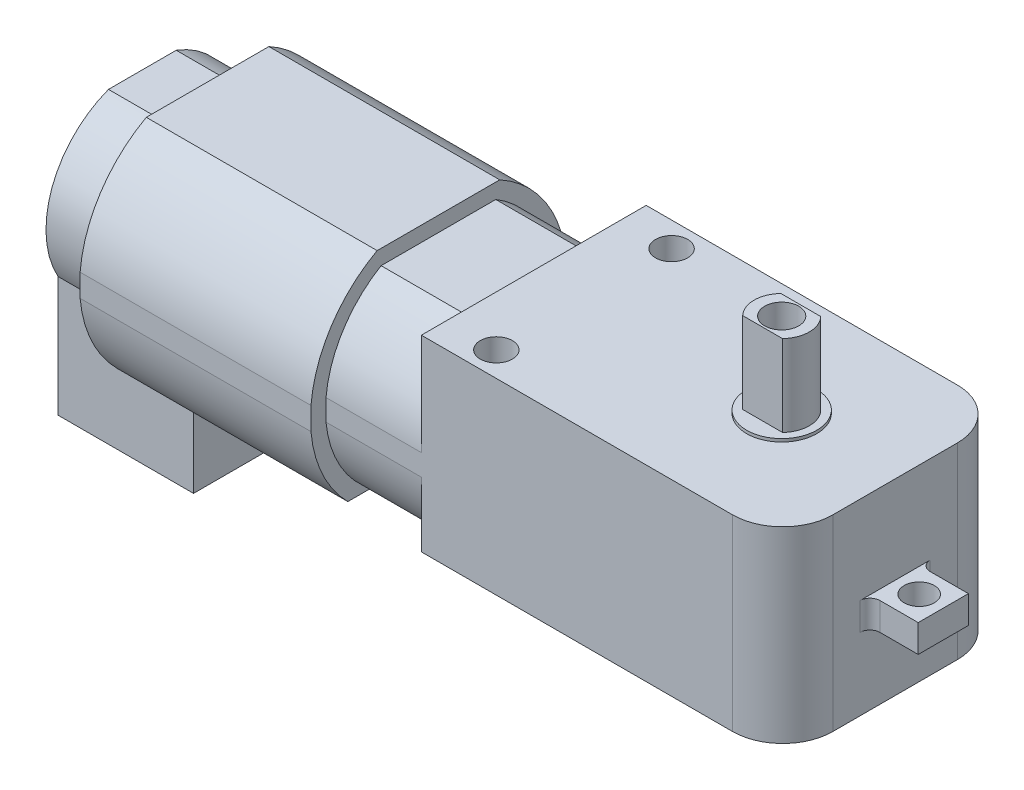
SolidWorks part; units mm, degrees
ref_plane "Front Plane" through (0, 0, 0) normal (0, 0, 1) x (1, 0, 0)
ref_plane "Top Plane" through (0, 0, 0) normal (0, 1, 0) x (1, 0, 0)
ref_plane "Right Plane" through (0, 0, 0) normal (1, 0, 0) x (0, 0, -1)
sketch "Sketch1" plane through (0, 0, 0) normal (0, 1, 0) x (1, 0, 0)
  line L0 (-13, -8.7312) -> (-13, 8.7312) construction
  line L1 (-18, -11.2) -> (18, -11.2)
  line L2 (-18, -11.2) -> (-18, 11.2)
  line L3 (-18, 11.2) -> (18, 11.2)
  line L4 (18, -11.2) -> (18, 11.2)
  line L5 (-18, -11.2) -> (18, 11.2) construction
  line L6 (-18, 11.2) -> (18, -11.2) construction
  circle A0 centre (-13, 8.7312) radius 1.6
  circle A1 centre (-13, -8.7312) radius 1.6
  point P0 (0, 0)
  point P8 (-13, 8.7312)
  point P9 (-13, 0)
  dimension "D3" = 3.2
  dimension "D1" = 36
  dimension "D2" = 22.4
  dimension "D4" = 31
  dimension "D5" = 8.7312
extrude "Boss-Extrude1" add sketch "Sketch1" along normal mid plane 18.7
fillet "Fillet1" radius 5 2 edges at (18, 0, 11.2) (18, 0, -11.2)
sketch "Sketch2" plane through (0, 9.35, 0) normal (0, 1, 0) x (1, 0, 0)
  line L0 (18, 0) -> (6.7, 0) construction
  line L1 (18, -6.2) -> (18, 6.2) construction
  circle A0 centre (6.7, 0) radius 3.5
  point P6 (10.2, 0)
  dimension "D1" = 7
  dimension "D2" = 7.8
extrude "Boss-Extrude2" add sketch "Sketch2" along normal blind 0.3
sketch "Sketch3" plane through (0, 9.65, 0) normal (0, 1, 0) x (1, 0, 0)
  line L0 (3.95, 0) -> (9.45, 0) construction
  line L1 (3.95, 1.905) -> (9.45, 1.905)
  line L2 (3.95, -1.905) -> (9.45, -1.905)
  circle A0 centre (6.7, 0) radius 2.75
  arc A1 (3.95, 1.905) -> (3.95, -1.905) centre (3.95, 0) ccw
  arc A2 (9.45, -1.905) -> (9.45, 1.905) centre (9.45, 0) ccw
  point P5 (6.7, 0)
  dimension "D1" = 5.5
  dimension "D2" = 3.81
extrude "Boss-Extrude4" add sketch "Sketch3" along normal offset from surface (8.4 mm away) 8.4 from surface contours A0 L0 L1 | L0 A0 L2 region at (6.7, 9.65, -0.9057) region at (6.7, 9.65, 0.9057) up to face at (6.7, 9.35, -3.5) offset beyond the face yes starting at face at (6.7, 9.35, -3.5)
sketch "Sketch4" plane through (0, 17.75, 0) normal (0, 1, 0) x (1, 0, 0)
  point P0 (6.7, 0)
hole_wizard "M3 Clearance Hole1" positions "3DSketch1" profile "Sketch6" hole size "M3" standard "ANSI Metric"
sketch3d "3DSketch1"
  point P0 (6.7, 17.75, 0)
sketch "Sketch6" plane through (6.7, 17.75, 0) normal (1, 0, 0) x (0, 0, 1)
  line L0 (0, 0) -> (0, 9.0215)
  line L1 (0, 9.0215) -> (1.7, 8)
  line L2 (1.7, 8) -> (1.7, 0)
  line L5 (1.7, 0) -> (0, 0)
  line L10 (0, 9.0215) -> (-1.7, 8) construction
  line L11 (0, -6.35) -> (0, 107.95) construction
  dimension "Hole Dia." = 3.4
  dimension "Hole Depth" = 8
  dimension "Drill Angle" = 118
sketch "Sketch7" plane through (-18, 0, 0) normal (-1, 0, 0) x (0, 0, 1)
  line L0 (11.2, 9.35) -> (11.2, -9.35) construction
  line L1 (-11.2, -9.35) -> (11.2, -9.35)
  line L2 (-11.2, -9.35) -> (-11.2, 7.85)
  line L3 (-11.2, 7.85) -> (11.2, 7.85)
  line L4 (11.2, -9.35) -> (11.2, 7.85)
  circle A0 centre (0, -1.8422) radius 11.25
  dimension "D2" = 22.5
  dimension "D1" = 17.2
extrude "Boss-Extrude5" add sketch "Sketch7" along normal blind 9.5 contours L4 A0 L3 L2 L1 region at (-18, -1.059, 0)
sketch "Sketch8" plane through (-27.5, 0, 0) normal (-1, 0, 0) x (0, 0, 1)
  line L8 (12.7, -2.9702) -> (12.7, -0.7141)
  line L9 (6.1072, 9.35) -> (-6.1072, 9.35)
  line L10 (-12.7, -0.7141) -> (-12.7, -2.9702)
  line L11 (-9.0234, -10.85) -> (9.0234, -10.85)
  line L12 (12.7, -2.9702) -> (12.7, -0.7141)
  line L13 (6.1072, 9.35) -> (-6.1072, 9.35)
  line L14 (-12.7, -0.7141) -> (-12.7, -2.9702)
  line L15 (-9.0234, -10.85) -> (9.0234, -10.85)
  arc A8 (12.7, -0.7141) -> (6.1072, 9.35) centre (0, -1.8422) ccw
  arc A9 (-6.1072, 9.35) -> (-12.7, -0.7141) centre (0, -1.8422) ccw
  arc A10 (-12.7, -2.9702) -> (-9.0234, -10.85) centre (0, -1.8422) ccw
  arc A11 (9.0234, -10.85) -> (12.7, -2.9702) centre (0, -1.8422) ccw
  arc A12 (12.7, -0.7141) -> (6.1072, 9.35) centre (0, -1.8422) ccw
  arc A13 (-6.1072, 9.35) -> (-12.7, -0.7141) centre (0, -1.8422) ccw
  arc A14 (-12.7, -2.9702) -> (-9.0234, -10.85) centre (0, -1.8422) ccw
  arc A15 (9.0234, -10.85) -> (12.7, -2.9702) centre (0, -1.8422) ccw
  dimension "D1" = 1.5
extrude "Boss-Extrude6" add sketch "Sketch8" along normal offset from surface (23 mm away) 68.5 up to face at (18, 0, 0)
ref_plane "Plane1" through (-57, 0, 0) normal (1, 0, 0) x (0, 0, -1)
sketch "Sketch9" plane through (-57, 0, 0) normal (-1, 0, 0) x (0, 0, 1)
  line L0 (-3.375, 7.145) -> (3.375, 7.145)
  line L1 (-8.4, -1.8422) -> (8.4, -1.8422)
  line L2 (-8.4, -1.8422) -> (-8.4, -18.455)
  line L3 (-8.4, -18.455) -> (8.4, -18.455)
  line L4 (8.4, -1.8422) -> (8.4, -18.455)
  circle A0 centre (0, -1.8422) radius 9.6
  point P7 (0, -1.8422)
  dimension "D2" = 19.2
  dimension "D1" = 6.75
  dimension "D3" = 25.6
  dimension "D4" = 16.8
extrude "Boss-Extrude7" add sketch "Sketch9" against normal blind 13.5 contours A0 L2 L1 L4 | L2 A0 L4 L3 | A0 L4 L1 L2 L0 region at (-57, 1.8425, 0) region at (-57, -14.1194, 0) region at (-57, -6.0437, 0)
sketch "Sketch11" plane through (0, -18.455, 0) normal (0, -1, 0) x (1, 0, 0)
  line L0 (-43.5, 8.4) -> (-43.5, -8.4) construction
  line L1 (-46.5, 6.7) -> (-50.4, 6.7)
  line L2 (-46.5, 6.7) -> (-46.5, -6.7)
  line L3 (-46.5, -6.7) -> (-50.4, -6.7)
  line L4 (-50.4, 6.7) -> (-50.4, -6.7)
  point P6 (-46.5, 0)
  dimension "D1" = 3
  dimension "D2" = 13.4
  dimension "D3" = 3.9
extrude "Cut-Extrude1" cut sketch "Sketch11" against normal blind 5
ref_plane "Plane2" through (0, -2.15, 0) normal (0, -1, 0) x (-1, 0, 0)
sketch "Sketch13" plane through (0, -2.15, 0) normal (0, 1, 0) x (1, 0, 0)
  line L0 (18, -6.2) -> (18, 6.2) construction
  line L1 (22.8, 2.5) -> (18, 2.5)
  line L2 (22.8, 2.5) -> (22.8, -2.5)
  line L3 (22.8, -2.5) -> (18, -2.5)
  line L4 (18, 2.5) -> (18, -2.5)
  line L5 (22.8, 2.5) -> (18, -2.5) construction
  line L6 (22.8, -2.5) -> (18, 2.5) construction
  circle A0 centre (20.4, 0) radius 1.5
  dimension "D3" = 3
  dimension "D1" = 5
  dimension "D2" = 4.8
extrude "Boss-Extrude8" add sketch "Sketch13" along normal blind 2.75
fillet "Fillet2" radius 1 2 edges at (18, -0.775, -2.5) (18, -0.775, 2.5)
ref_axis "Axis1" through (6.7, 17.75, 0) along (0, -1, 0)
